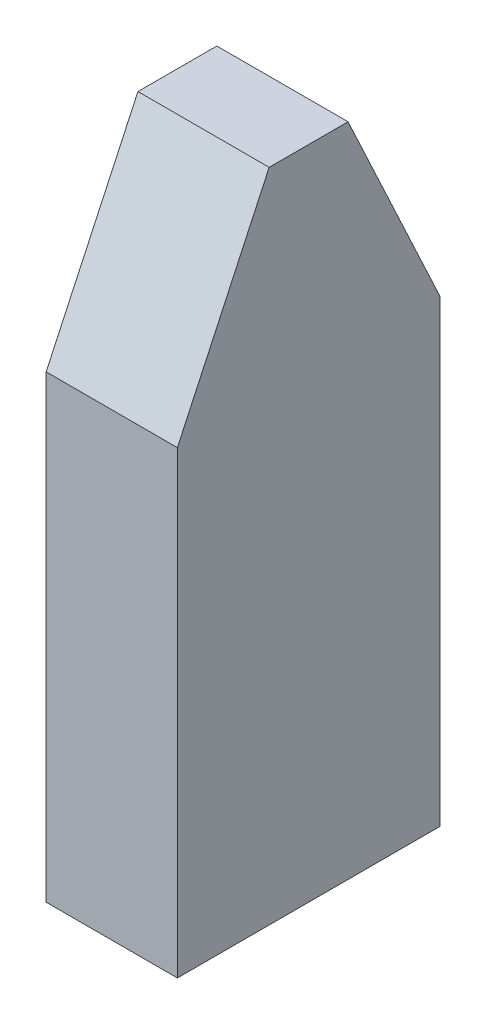
SolidWorks part; units mm, degrees
material "кварц кристаллический"
ref_plane "Спереди" through (0, 0, 0) normal (0, 0, 1) x (1, 0, 0)
ref_plane "Сверху" through (0, 0, 0) normal (0, 1, 0) x (1, 0, 0)
ref_plane "Справа" through (0, 0, 0) normal (1, 0, 0) x (0, 0, -1)
ref_axis "Ось1" through (-11, 0, 0) along (1, 0, 0)
ref_plane "Плоскость1" through (0, 0, 0) normal (0, 0.3173, -0.9483) x (-1, 0, 0)
sketch "Эскиз1" plane through (0, 0, 0) normal (0, 1, 0) x (1, 0, 0)
  line L0 (5, 10) -> (-5, -10) construction
  line L1 (-5, 10) -> (5, 10)
  line L2 (-5, 10) -> (-5, -10)
  line L3 (-5, -10) -> (5, -10)
  line L4 (5, 10) -> (5, -10)
  line L5 (-5, 10) -> (5, -10) construction
  dimension "D1" = 20
  dimension "D2" = 10
extrude "Вытянуть1" add sketch "Эскиз1" along normal blind 50
chamfer "Фаска1" distance 15 angle 25 1 edges at (0, 50, 10) first distance on face at (0, 25, 10)
chamfer "Фаска2" distance 15 angle 25 1 edges at (0, 50, -10) first distance on face at (0, 25, -10)
sketch3d "Трехмерный эскиз1"
  point P0 (0, 25, 0)
  dimension "D1" = 25
